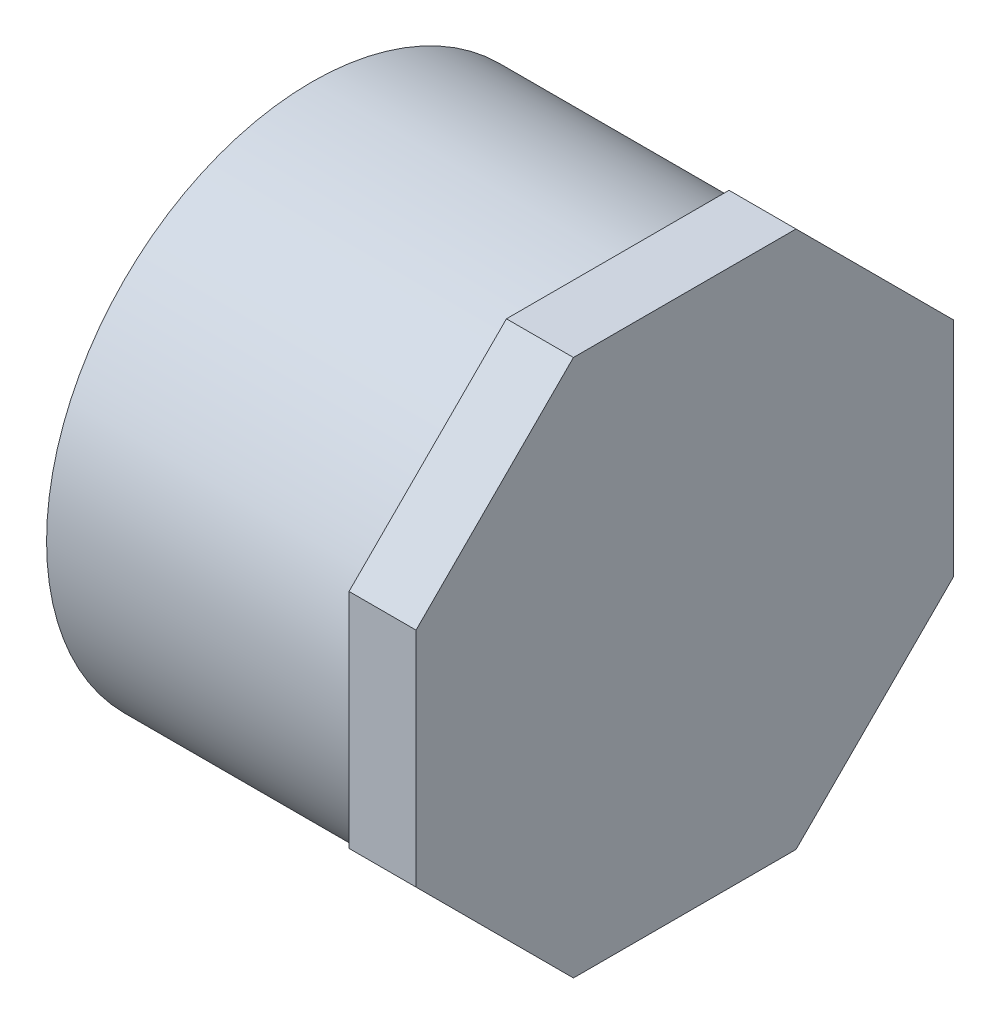
SolidWorks part; units mm, degrees
ref_plane "Front Plane" through (0, 0, 0) normal (0, 0, 1) x (1, 0, 0)
ref_plane "Top Plane" through (0, 0, 0) normal (0, 1, 0) x (1, 0, 0)
ref_plane "Right Plane" through (0, 0, 0) normal (1, 0, 0) x (0, 0, -1)
sketch "Sketch0" plane through (0, 0, 0) normal (0, 0, 1) x (1, 0, 0)
  line L2 (-21.209, 30.1625) -> (-21.209, -30.1625) construction
  line L3 (-21.209, 0) -> (21.209, 0) construction
  line L14 (13.589, 26.2509) -> (13.589, -26.2509) construction
  point P5 (13.589, 0)
  dimension "ID" = 52.5018
  dimension "L" = 42.418
  dimension "C" = 34.798
  dimension "Pipe OD" = 60.325
  dimension "R" = 7.62
  dimension "Wall Thickness" = 3.9116
sketch "Sketch1" plane through (0, 0, 0) normal (0, 0, 1) x (1, 0, 0)
  line L0 (-21.209, -30.1625) -> (21.209, -30.1625)
  line L1 (-21.209, 0) -> (21.209, 0) construction
  line L3 (21.209, 0) -> (13.589, 0)
  line L4 (13.589, -26.2509) -> (-21.209, -26.2509)
  line L5 (-21.209, -26.2509) -> (-21.209, -30.1625)
  line L6 (-21.209, 30.1625) -> (-21.209, -30.1625) construction
  line L7 (21.209, 0) -> (21.209, -30.1625)
  line L10 (13.589, 0) -> (13.589, -26.2509)
revolve "Revolve1" add sketch "Sketch1" angle 360 about L1
sketch "Sketch2" plane through (21.209, 0, 0) normal (1, 0, 0) x (0, 0, -1)
  line L0 (0, 35.2869) -> (0, 0) construction
  line L1 (0, 35.2869) -> (-30.5594, 17.6435) construction
  line L2 (-30.5594, 17.6435) -> (-30.5594, -17.6435) construction
  line L3 (-30.5594, -17.6435) -> (0, -35.2869) construction
  line L4 (0, -35.2869) -> (30.5594, -17.6435) construction
  line L5 (30.5594, -17.6435) -> (30.5594, 17.6435) construction
  line L6 (30.5594, 17.6435) -> (0, 35.2869) construction
  line L8 (-12.6581, 30.5594) -> (-30.5594, 12.6581)
  line L9 (-30.5594, 12.6581) -> (-30.5594, -12.6581)
  line L10 (-30.5594, -12.6581) -> (-12.6581, -30.5594)
  line L11 (-12.6581, -30.5594) -> (12.6581, -30.5594)
  line L12 (12.6581, -30.5594) -> (30.5594, -12.6581)
  line L13 (30.5594, -12.6581) -> (30.5594, 12.6581)
  line L14 (30.5594, 12.6581) -> (12.6581, 30.5594)
  line L15 (12.6581, 30.5594) -> (-12.6581, 30.5594)
  circle A0 centre (0, 0) radius 30.1625 construction
  circle A1 centre (0, 0) radius 30.1625
  circle A2 centre (0, 0) radius 30.5594 construction
  circle A3 centre (0, 0) radius 30.5594 construction
  dimension "D1" = 61.1187
extrude "Boss-Extrude1" add sketch "Sketch2" against normal up to vertex (7.62 mm away) up to point (13.589, 0, 0)
other "CPoint1" parameters "Diameter"=50.8, "StubLength"=228.6
ref_axis "Axis1" through (3.589, 0, 0) along (1, 0, 0)
other "RPoint1"
ref_axis "Axis of Rotation" through (13.589, 0, 0) along (-1, 0, 0)
scale "Scale1" scale about centroid uniform scaling yes scale factor 0.41
